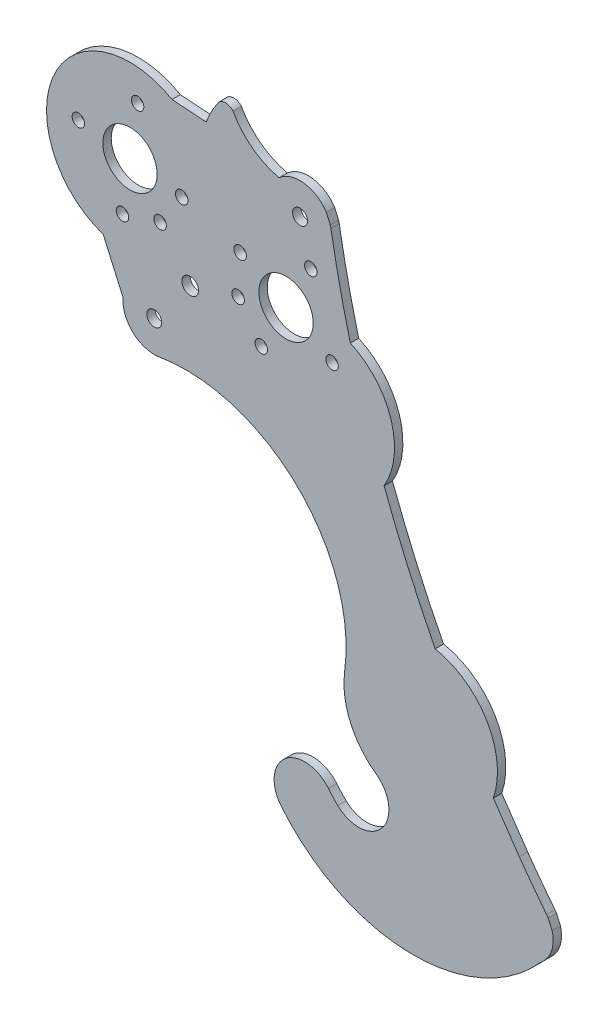
SolidWorks part; units mm, degrees
note: The reader was unsure of these and kept them because the rebuilt part matched: shared geometry of "Sketch9<3>", "Sketch16<3>", "Sketch17<2>", "Sketch20<3>".
material "Plain Carbon Steel"
ref_plane "Front Plane" through (0, 0, 0) normal (0, 0, 1) x (1, 0, 0)
ref_plane "Top Plane" through (0, 0, 0) normal (0, 1, 0) x (1, 0, 0)
ref_plane "Right Plane" through (0, 0, 0) normal (1, 0, 0) x (0, 0, -1)
sketch "Sketch1" plane through (0, 0, 0) normal (0, 0, 1) x (1, 0, 0)
  line L0 (214.9509, 33.6169) -> (221.8072, 36.6569)
  line L1 (221.8072, 36.6569) -> (220.1858, 40.3136)
  line L2 (249.0335, 53.1046) -> (220.1858, 40.3136)
  line L3 (211.0442, 36.2602) -> (218.8806, 18.5866)
  line L4 (213.3296, 37.2735) -> (214.9509, 33.6169)
  line L5 (279.2963, 23.754) -> (254.3124, 52.9018)
  line L6 (223.5, 15.5) -> (275.5, 15.5)
  line L7 (213.3296, 37.2735) -> (211.0442, 36.2602)
  circle A1 centre (275.5, 20.5) radius 1.8
  arc A3 (218.8806, 18.5866) -> (223.5, 15.5) centre (223.5, 20.5) ccw
  circle A4 centre (251.5, 48.5) radius 2.75
  circle A5 centre (223.5, 20.5) radius 1.8
  arc A6 (254.3124, 52.9018) -> (249.0335, 53.1046) centre (251.5791, 50.559) ccw
  arc A7 (275.5, 15.5) -> (279.2963, 23.754) centre (275.5, 20.5) ccw
  dimension "D1" = 5.5
  dimension "D2" = 7.5
  dimension "D3" = 4
extrude "Extrude2" add sketch "Sketch1" along normal blind 2
sketch "Sketch2" plane through (0, 0, 2) normal (0, 0, 1) x (1, 0, 0)
  line L0 (211.0442, 36.2602) -> (218.8806, 18.5866)
  line L1 (211.0442, 36.2602) -> (275.0358, 64.6339)
  line L2 (218.8806, 18.5866) -> (285.1898, 47.9879)
  line L3 (295.3028, 18.9256) -> (275.0358, 64.6339)
  line L4 (285.1898, 47.9879) -> (256.0904, 35.0853)
  line L6 (256.0904, 35.0853) -> (268.5209, 7.0506)
  line L7 (295.3028, 18.9256) -> (268.5209, 7.0506)
  circle A1 centre (256.1616, 71.063) radius 65.1946
  dimension "D1" = 50
  dimension "D2" = 70
extrude "Extrude3" add sketch "Sketch2" against normal blind 2
ref_plane "Plane1" through (11.1049, -25.045, 0) normal (-0.4053, 0.9142, 0) x (-0.9142, -0.4053, 0)
mirror "Mirror2" about plane through (11.1049, -25.045, 0) normal (-0.4053, 0.9142, 0) of bodies 102 103
sketch "Sketch3" plane through (0, 0, 2) normal (0, 0, 1) x (1, 0, 0)
  line L0 (275.0358, 64.6339) -> (254.7689, 110.3422)
  line L1 (211.0442, 36.2602) -> (190.7772, 81.9685)
  line L2 (190.7772, 81.9685) -> (199.9189, 86.0219)
  line L3 (199.9189, 86.0219) -> (220.1858, 40.3136)
  line L4 (220.1858, 40.3136) -> (211.0442, 36.2602)
  line L5 (211.0442, 36.2602) -> (210.9159, 37.0193)
  line L6 (220.1858, 40.3136) -> (275.0358, 64.6339)
  line L7 (199.9189, 86.0219) -> (254.7689, 110.3422)
  line L8 (234.5019, 156.0506) -> (254.7689, 110.3422) construction
extrude "Extrude4" add sketch "Sketch3" against normal blind 2
sketch "Sketch4" plane through (0, 0, 2) normal (0, 0, 1) x (1, 0, 0)
  line L0 (295.3028, 18.9256) -> (234.5019, 156.0506) construction
  line L1 (262.4068, 78.1774) -> (258.7501, 76.556)
  line L2 (262.4068, 78.1774) -> (256.3267, 91.8899)
  line L3 (256.3267, 91.8899) -> (252.67, 90.2685)
  line L4 (258.7501, 76.556) -> (252.67, 90.2685)
  line L5 (286.7271, 23.3274) -> (283.0705, 21.706)
  line L6 (286.7271, 23.3274) -> (280.647, 37.0399)
  line L7 (280.647, 37.0399) -> (276.9904, 35.4185)
  line L8 (283.0705, 21.706) -> (276.9904, 35.4185)
  line L9 (234.4298, 131.406) -> (238.0864, 133.0273)
  line L10 (234.4298, 131.406) -> (228.3497, 145.1185)
  line L11 (228.3497, 145.1185) -> (232.0064, 146.7398)
  line L12 (238.0864, 133.0273) -> (232.0064, 146.7398)
  line L14 (256.3267, 91.8899) -> (238.0864, 133.0273) construction
  line L15 (262.4068, 78.1774) -> (280.647, 37.0399) construction
  line L16 (264.9023, 87.4881) -> (200.9107, 59.1144) construction
  line L17 (182.9408, 99.6421) -> (218.8806, 18.5866) construction
  line L18 (255.7101, 83.4123) -> (259.3667, 85.0336) construction
  circle A2 centre (227.0101, 103.7323) radius 2.75 construction
  dimension "D5" = 18
  dimension "D2" = 45
  dimension "D3" = 4
  dimension "D4" = 15
extrude "Extrude5" cut sketch "Sketch4" against normal blind 10
sketch "Sketch5" plane through (0, 0, 2) normal (0, 0, 1) x (1, 0, 0)
  line L0 (251.5, 48.5) -> (227.0101, 103.7323) construction
  circle A0 centre (239.2551, 76.1162) radius 3
extrude "Extrude6" cut sketch "Sketch5" against normal blind 55
sketch "Sketch8" plane through (0, 0, 0) normal (0, 0, -1) x (-1, 0, 0)
  line L0 (-198.7245, 91.591) -> (-189.7673, 87.7708)
  line L1 (-198.7245, 91.591) -> (-219.7201, 42.3643)
  line L2 (-189.7673, 87.7708) -> (-210.763, 38.544)
  line L3 (-219.7201, 42.3643) -> (-210.763, 38.544)
extrude "Boss-Extrude2" add sketch "Sketch8" against normal blind 2
sketch "Sketch6" plane through (0, 0, 2) normal (0, 0, 1) x (1, 0, 0)
  line L0 (215.3057, 32.6803) -> (222.1619, 35.7203)
  line L1 (215.3057, 32.6803) -> (213.6843, 36.3369)
  line L2 (222.1619, 35.7203) -> (220.5406, 39.377)
  line L3 (213.6843, 36.3369) -> (220.5406, 39.377)
  line L4 (220.1858, 40.3136) -> (213.3296, 37.2735) construction
  line L6 (276.9904, 35.4185) -> (283.0705, 21.706) construction
  line L7 (258.7501, 76.556) -> (262.4068, 78.1774) construction
  dimension "D1" = 18.5
  dimension "D2" = 4
  dimension "D3" = 7.5
  dimension "D4" = 50
extrude "Cut-Extrude2" cut sketch "Sketch6" against normal blind 10
sketch "Sketch7" plane through (0, 0, 0) normal (0, 0, -1) x (-1, 0, 0)
  line L0 (-222.1619, 35.7203) -> (-215.3057, 32.6803)
  line L1 (-222.1619, 35.7203) -> (-220.5406, 39.377)
  line L2 (-215.3057, 32.6803) -> (-213.6843, 36.3369)
  line L3 (-220.5406, 39.377) -> (-213.6843, 36.3369)
  line L4 (-222.1619, 35.7203) -> (-221.7566, 36.6345) construction
  line L5 (-215.3057, 32.6803) -> (-222.1619, 35.7203) construction
  line L6 (-213.7349, 36.3594) -> (-213.6843, 36.3369) construction
  line L7 (-211.7989, 37.4505) -> (-220.5406, 42.0862)
  line L8 (-211.7989, 37.4505) -> (-215.828, 29.8527)
  line L9 (-220.5406, 42.0862) -> (-224.5697, 34.4884)
  line L10 (-215.828, 29.8527) -> (-224.5697, 34.4884)
mirror "Mirror3" about plane through (11.1049, -25.045, 0) normal (-0.4053, 0.9142, 0) of "Cut-Extrude2"
extrude "Boss-Extrude3" add sketch "Sketch7" against normal blind 2
sketch "Sketch9" plane through (0, 0, 0) normal (0, 0, -1) x (-1, 0, 0)
  circle A0 centre (-187.4603, 101.7809) radius 7.5
  circle A1 centre (-222.3731, 140.3178) radius 7.5
  circle A2 centre (-223.5, 20.5) radius 7.5
  circle A3 centre (-275.5, 20.5) radius 7.5
  circle A4 centre (-227.0101, 103.7323) radius 10
  circle A5 centre (-239.2551, 76.1162) radius 10
  circle A6 centre (-251.5, 48.5) radius 10
  arc A7 (-217.2457, 134.8443) -> (-192.4025, 107.4222) centre (-204.5955, 121.3403) ccw
  arc A8 (-188.6919, 94.3827) -> (-218.8442, 26.3799) centre (-194.9996, 56.4934) ccw
  arc A9 (-229.7628, 141.5991) -> (-281.411, 25.1162) centre (-487.8726, 186.3525) cw
  arc A10 (-230.999, 20.375) -> (-268.001, 20.375) centre (-249.5, 20.0666) ccw
  arc M7 (-182.5262, 102.5901) -> (-234.5019, 156.0506) centre (-246.8612, 92.0382) ccw
  line M8 (-234.5019, 156.0506) -> (-295.3028, 18.9256)
  arc M9 (-295.3028, 18.9256) -> (-220.787, 16.3) centre (-256.1616, 71.063) ccw
  arc M10 (-220.787, 16.3) -> (-218.8806, 18.5866) centre (-223.5, 20.5) ccw
  line M11 (-218.8806, 18.5866) -> (-182.9408, 99.6421)
  arc M12 (-182.9408, 99.6421) -> (-182.5262, 102.5901) centre (-187.4603, 101.7809) ccw
  line M13 (-258.7501, 76.556) -> (-262.4068, 78.1774)
  line M14 (-262.4068, 78.1774) -> (-256.3267, 91.8899)
  line M15 (-256.3267, 91.8899) -> (-252.67, 90.2685)
  line M16 (-252.67, 90.2685) -> (-258.7501, 76.556)
  line M17 (-283.0705, 21.706) -> (-286.7271, 23.3274)
  line M18 (-286.7271, 23.3274) -> (-280.647, 37.0399)
  line M19 (-280.647, 37.0399) -> (-276.9904, 35.4185)
  line M20 (-276.9904, 35.4185) -> (-283.0705, 21.706)
  line M21 (-232.0064, 146.7398) -> (-228.3497, 145.1185)
  line M22 (-228.3497, 145.1185) -> (-234.4298, 131.406)
  line M23 (-234.4298, 131.406) -> (-238.0864, 133.0273)
  line M24 (-238.0864, 133.0273) -> (-232.0064, 146.7398)
  line M26 (-190.9853, 87.5303) -> (-192.6067, 83.8736)
  line M27 (-192.6067, 83.8736) -> (-199.4629, 86.9136)
  line M28 (-199.4629, 86.9136) -> (-197.8416, 90.5703)
  line M29 (-197.8416, 90.5703) -> (-190.9853, 87.5303)
  line M30 (-222.1619, 35.7203) -> (-220.5406, 39.377)
  line M31 (-220.5406, 39.377) -> (-213.6843, 36.3369)
  line M32 (-213.6843, 36.3369) -> (-215.3057, 32.6803)
  line M33 (-215.3057, 32.6803) -> (-222.1619, 35.7203)
  dimension "D1" = 15
  dimension "D2" = 20
extrude "Cut-Extrude3" cut sketch "Sketch9" against normal blind 10 contours A2 A10 A3 A9 A1 A7 A0 M20 M17 M18 M19 M22 M23 M24 M21 M7 M8 M9 M16 M13 M14 M15 | A0 A8 A2 M11 M33 M30 M31 M32 M29 M26 M27 M28
extrude "Boss-Extrude4" add sketch "Sketch9<3>" against normal blind 2 contours A0 M11 M7 M12 | A2 M9 M11 M10
sketch "Sketch9<3>" plane through (0, 0, 0) normal (0, 0, -1) x (-1, 0, 0) same geometry as "Sketch9"
sketch "Sketch10" plane through (0, 0, 0) normal (0, 0, -1) x (-1, 0, 0)
  line L0 (-187.4603, 101.7809) -> (-223.5, 20.5) construction
  line L1 (-223.5, 20.5) -> (-205.4801, 61.1404) construction
  line L2 (-205.4801, 61.1404) -> (-258.1527, 84.4953) construction
  arc A0 (-211.0121, 103.9849) -> (-222.9768, 119.2156) centre (-227.0101, 103.7323) ccw construction
  arc A1 (-209.0138, 103.3719) -> (-223.0991, 121.3023) centre (-227.0101, 103.7323) ccw
  arc A2 (-213.0577, 104.885) -> (-222.5865, 117.0151) centre (-227.0101, 103.7323) ccw
  arc A3 (-223.0991, 121.3023) -> (-222.5865, 117.0151) centre (-204.5955, 121.3403) ccw
  circle A4 centre (-227.0101, 103.7323) radius 18 construction
  circle A5 centre (-227.0101, 103.7323) radius 16 construction
  circle A6 centre (-227.0101, 103.7323) radius 14 construction
  arc A7 (-213.0577, 104.885) -> (-209.0138, 103.3719) centre (-204.5955, 121.3403) ccw
  arc A8 (-240.9461, 36.4744) -> (-260.2666, 35.1154) centre (-251.5, 48.5) cw construction
  arc A9 (-242.9866, 37.386) -> (-239.1501, 35.4049) centre (-249.5, 20.0666) cw
  arc A10 (-261.8951, 33.8051) -> (-258.3738, 36.3036) centre (-249.5, 20.0666) cw
  arc A11 (-242.9866, 37.386) -> (-258.3738, 36.3036) centre (-251.5, 48.5) cw
  arc A12 (-239.1501, 35.4049) -> (-261.8951, 33.8051) centre (-251.5, 48.5) cw
  arc A13 (-234.4184, 120.1371) -> (-242.5117, 94.5835) centre (-227.0101, 103.7323) ccw
  arc A14 (-235.9587, 114.499) -> (-240.5254, 100.0803) centre (-227.0101, 103.7323) ccw
  arc A15 (-281.411, 25.1162) -> (-229.7628, 141.5991) centre (-487.8726, 186.3525) ccw construction
  arc A16 (-268.6314, 42.976) -> (-255.1276, 66.1307) centre (-251.5, 48.5) cw
  arc A17 (-213.0577, 104.885) -> (-222.5865, 117.0151) centre (-227.0101, 103.7323) ccw
  arc A18 (-209.0138, 103.3719) -> (-223.0991, 121.3023) centre (-227.0101, 103.7323) ccw
  arc A19 (-265.4873, 47.903) -> (-257.8677, 60.9681) centre (-251.5, 48.5) cw
  arc A20 (-235.9587, 114.499) -> (-234.4184, 120.1371) centre (-239.2163, 118.4185) ccw
  arc A21 (-242.5117, 94.5835) -> (-240.5254, 100.0803) centre (-244.8427, 98.5331) ccw
  arc A22 (-257.8677, 60.9681) -> (-255.1276, 66.1307) centre (-260.1858, 65.5068) ccw
  arc A23 (-268.6314, 42.976) -> (-265.4873, 47.903) centre (-265.0225, 44.1397) ccw
  arc M4 (-192.4025, 107.4222) -> (-217.2457, 134.8443) centre (-204.5955, 121.3403) cw
  arc M12 (-268.001, 20.375) -> (-230.999, 20.375) centre (-249.5, 20.0666) cw
  dimension "D1" = 32
  dimension "D2" = 2
  dimension "D3" = 2
extrude "Boss-Extrude5" add sketch "Sketch10" against normal blind 2 contours A14 A20 A13 A21 | A2 A1 M4 | A12 A11 M12 | A23 A19 A22 A16
sketch "Sketch11" plane through (0, 0, 0) normal (0, 0, -1) x (-1, 0, 0)
  line L0 (-215.1923, 111.2382) -> (-221.6681, 90.7916) construction
  line L1 (-226.4188, 89.7448) -> (-244.17, 109.1672) construction
  line L2 (-244.17, 109.1672) -> (-218.4742, 114.829) construction
  line L3 (-227.0101, 103.7323) -> (-233.6834, 105.8459) construction
  arc A1 (-213.0586, 104.8959) -> (-224.5994, 117.5232) centre (-227.0101, 103.7323) ccw
  arc A2 (-216.2723, 94.7491) -> (-232.9782, 91.0681) centre (-223.1369, 86.154) ccw
  arc A3 (-224.5994, 117.5232) -> (-213.0586, 104.8959) centre (-213.7235, 115.8758) ccw
  arc A4 (-240.1588, 98.9246) -> (-234.9936, 115.2329) centre (-244.17, 109.1672) ccw
  arc A5 (-209.0138, 103.3719) -> (-223.0991, 121.3023) centre (-227.0101, 103.7323) ccw construction
  arc A6 (-232.9782, 91.0681) -> (-216.2723, 94.7491) centre (-227.0101, 103.7323) ccw
  arc A7 (-234.9936, 115.2329) -> (-240.1588, 98.9246) centre (-227.0101, 103.7323) ccw
  circle A8 centre (-227.0101, 103.7323) radius 3
  dimension "D2" = 6
  dimension "D1" = 7
extrude "Cut-Extrude4" cut sketch "Sketch11" against normal blind 10
sketch "Sketch13" plane through (0, 0, 0) normal (0, 0, -1) x (-1, 0, 0)
  line L0 (-220.2817, 120.4274) -> (-222.3731, 140.3178) construction
  line L1 (-222.3731, 140.3178) -> (-207.2338, 151.3182) construction
  line L2 (-220.2817, 120.4274) -> (-215.284, 117.3887)
  line L3 (-230.0726, 145.8144) -> (-230.0212, 145.9081)
  line L4 (-230.0726, 145.8144) -> (-234.4184, 120.1371)
  line L5 (-234.4184, 120.1371) -> (-227.995, 140.6634)
  arc A0 (-217.6542, 118.8298) -> (-204.5753, 153.2498) centre (-222.3731, 140.3178) ccw construction
  arc A1 (-204.5753, 153.2498) -> (-230.0726, 145.8144) centre (-221.0416, 162.2808) cw construction
  arc A2 (-215.284, 117.3887) -> (-202.9573, 154.4255) centre (-222.3731, 140.3178) ccw
  arc A3 (-206.3289, 154.2116) -> (-227.4981, 146.7924) centre (-221.0416, 162.2808) cw
  arc A4 (-220.2817, 120.4274) -> (-203.346, 146.4798) centre (-222.3731, 140.3178) ccw
  arc A5 (-206.3289, 154.2116) -> (-229.1109, 147.568) centre (-221.0416, 162.2808) cw construction
  arc A6 (-209.0138, 103.3719) -> (-223.0991, 121.3023) centre (-227.0101, 103.7323) ccw construction
  circle A7 centre (-222.3731, 140.3178) radius 24 construction
  circle A8 centre (-222.3731, 140.3178) radius 22 construction
  circle A9 centre (-222.3731, 140.3178) radius 20 construction
  arc A10 (-202.9573, 154.4255) -> (-206.3289, 154.2116) centre (-204.5361, 152.6327) ccw
  arc A11 (-206.6353, 147.3049) -> (-225.6434, 142.0164) centre (-221.0416, 162.2808) cw
  arc A12 (-230.0212, 145.9081) -> (-227.4981, 146.7924) centre (-228.2677, 144.9463) cw
  arc A13 (-203.346, 146.4798) -> (-206.6353, 147.3049) centre (-205.2487, 145.8636) ccw
  arc A14 (-225.6434, 142.0164) -> (-227.995, 140.6634) centre (-226.0863, 140.0661) ccw
  circle M8 centre (-222.3731, 140.3178) radius 1.8
  arc M27 (-209.0138, 103.3719) -> (-223.0991, 121.3023) centre (-227.0101, 103.7323) ccw
  arc M29 (-217.2457, 134.8443) -> (-228.6758, 144.3831) centre (-222.3731, 140.3178) ccw
  line M30 (-228.6758, 144.3831) -> (-229.6175, 142.2592)
  arc M31 (-229.6175, 142.2592) -> (-229.7628, 141.5991) centre (-222.3731, 140.3178) ccw
  arc M32 (-229.7628, 141.5991) -> (-234.4184, 120.1371) centre (-487.8726, 186.3525) cw
  dimension "D1" = 44
  dimension "D2" = 2
  dimension "D6" = 2
  dimension "D5" = 120
  dimension "D3" = 2
  dimension "D4" = 2
extrude "Boss-Extrude6" add sketch "Sketch13" against normal blind 2 contours A14 A11 A3 L5 M8 M29 M30 M31 M32 | A13 A4 A2 A10 A3 A11 M27 M29
sketch "Sketch14" plane through (0, 0, 0) normal (0, 0, -1) x (-1, 0, 0)
  line L0 (-204.6205, 124.1671) -> (-201.4385, 128.5814)
  line L1 (-187.4603, 109.2809) -> (-192.368, 107.4522)
  arc A0 (-187.4603, 109.2809) -> (-201.4385, 128.5814) centre (-176.6451, 131.8258) cw
  arc A1 (-188.6919, 94.3827) -> (-192.4025, 107.4222) centre (-187.4603, 101.7809) ccw construction
  arc A3 (-192.368, 107.4522) -> (-204.6205, 124.1671) centre (-176.6451, 131.8258) cw
  arc A4 (-187.4603, 109.2809) -> (-199.8399, 141.166) centre (-176.6451, 131.8258) cw construction
  arc A5 (-189.1904, 105.6744) -> (-203.5504, 142.6601) centre (-176.6451, 131.8258) cw construction
  dimension "D1" = 4
extrude "Boss-Extrude7" add sketch "Sketch14" against normal blind 2
mirror "Mirror5" about plane through (11.1049, -25.045, 0) normal (-0.4053, 0.9142, 0) of "Cut-Extrude4", "Boss-Extrude6", "Boss-Extrude7"
sketch "Sketch16" plane through (0, 0, 0) normal (0, 0, -1) x (-1, 0, 0)
  line L0 (-227.0101, 103.7323) -> (-196.0677, 112.8223)
  circle A0 centre (-196.0677, 112.8223) radius 2
  circle A1 centre (-187.4603, 101.7809) radius 1.8 construction
  circle A2 centre (-196.0677, 112.8223) radius 3.3422
  dimension "D2" = 4
  dimension "D3" = 14
  dimension "D1" = 32.25
extrude "Boss-Extrude8" add sketch "Sketch16" against normal blind 2
extrude "Cut-Extrude5" cut sketch "Sketch16<3>" against normal blind 2
sketch "Sketch16<3>" plane through (0, 0, 0) normal (0, 0, -1) x (-1, 0, 0) same geometry as "Sketch16"
sketch "Sketch17" plane through (0, 0, 0) normal (0, 0, -1) x (-1, 0, 0)
  line L0 (-227.0101, 103.7323) -> (-251.5, 48.5) construction
  line L1 (-204.6076, 125.0508) -> (-197.9558, 111.3332)
  line L2 (-197.9558, 111.3332) -> (-189.8837, 107.7486)
  line L3 (-191.7097, 149.3004) -> (-199.8952, 148.7288)
  line L4 (-189.8837, 107.7486) -> (-207.1736, 97.4)
  line L5 (-207.1736, 97.4) -> (-213.2426, 101.1916)
  line L6 (-204.6076, 125.0508) -> (-199.8952, 145.4392)
  line L7 (-175.2396, 113.0687) -> (-179.9834, 102.3699)
  line L8 (-196.0677, 112.8223) -> (-181.6542, 132.0121) construction
  line L9 (-199.8952, 145.4392) -> (-204.2733, 150.4745)
  line L10 (-204.2733, 150.4745) -> (-216.9035, 142.2081)
  line L11 (-216.9035, 142.2081) -> (-223.5, 134.1176)
  line L12 (-196.0677, 112.8223) -> (-188.8609, 122.4172) construction
  line L13 (-196.0677, 112.8223) -> (-207.5488, 116.3127) construction
  circle A0 centre (-181.6542, 132.0121) radius 12.5 construction
  circle A1 centre (-179.8489, 119.6432) radius 1.5
  circle A2 centre (-194.0231, 130.2069) radius 1.5
  circle A3 centre (-183.4594, 144.3811) radius 1.5
  circle A4 centre (-169.2852, 133.8174) radius 1.5
  arc A5 (-175.2396, 113.0687) -> (-191.7097, 149.3004) centre (-181.6542, 132.0121) ccw
  circle A6 centre (-181.6542, 132.0121) radius 6.5
  circle A7 centre (-187.4603, 101.7809) radius 1.8
  circle A8 centre (-196.0677, 112.8223) radius 2
  circle A9 centre (-222.3731, 140.3178) radius 1.8
  circle A10 centre (-223.5, 20.5) radius 1.8
  circle A11 centre (-275.5, 20.5) radius 1.8
  circle A17 centre (-188.8609, 122.4172) radius 1.5
  circle A18 centre (-207.5488, 116.3127) radius 1.5
  circle A19 centre (-208.0244, 125.73) radius 1.5
  circle A20 centre (-213.1032, 108.7976) radius 1.5
  circle A21 centre (-230.0356, 113.8764) radius 1.5
  circle A22 centre (-224.9568, 130.8088) radius 1.5
  circle A23 centre (-219.03, 119.8032) radius 6.5
  arc A32 (-179.9834, 102.3699) -> (-187.4603, 109.2809) centre (-187.4603, 101.7809) ccw
  arc A33 (-223.5, 134.1176) -> (-233.5627, 116.1042) centre (-219.03, 119.8032) ccw
  circle A35 centre (-239.2551, 76.1162) radius 3
  circle A36 centre (-251.5, 48.5) radius 14
  arc A37 (-201.4385, 128.5814) -> (-202.9573, 154.4255) centre (-222.3731, 140.3178) ccw
  arc A38 (-201.4385, 128.5814) -> (-196.1372, 116.1638) centre (-176.6451, 131.8258) ccw
  arc A39 (-192.7285, 112.6799) -> (-196.1372, 116.1638) centre (-196.0677, 112.8223) ccw
  arc A40 (-192.7285, 112.6799) -> (-187.4603, 109.2809) centre (-176.6451, 131.8258) ccw
  arc A41 (-188.6919, 94.3827) -> (-187.4603, 109.2809) centre (-187.4603, 101.7809) ccw
  arc A42 (-201.4385, 128.5814) -> (-199.8952, 148.7288) centre (-222.3731, 140.3178) ccw
  arc A43 (-201.4385, 128.5814) -> (-196.1372, 116.1638) centre (-176.6451, 131.8258) ccw
  arc A44 (-192.7285, 112.6799) -> (-196.1372, 116.1638) centre (-196.0677, 112.8223) ccw
  arc A45 (-192.7285, 112.6799) -> (-187.4603, 109.2809) centre (-176.6451, 131.8258) ccw
  arc A46 (-233.5627, 116.1042) -> (-213.2426, 101.1916) centre (-227.0101, 103.7323) ccw
  point P10 (-239.2551, 76.1162)
  dimension "D3" = 25
  dimension "D4" = 3
  dimension "D6" = 40
  dimension "D7" = 13
  dimension "D10" = 3
  dimension "D1" = 30
  dimension "D2" = 24
  dimension "D9" = 0
  dimension "D12" = 110
  dimension "D5" = 4
  dimension "D11" = 2
extrude "Boss-Extrude9" add sketch "Sketch17" against normal blind 2
extrude "Cut-Extrude6" cut sketch "Sketch17<2>" against normal blind 2
sketch "Sketch17<2>" plane through (0, 0, 0) normal (0, 0, -1) x (-1, 0, 0) same geometry as "Sketch17"
sketch "Sketch20" plane through (0, 0, 0) normal (0, 0, -1) x (-1, 0, 0)
  line L0 (-268.6314, 42.976) -> (-280.1153, 26.2004)
  line L1 (-205.8019, 22.7166) -> (-233.0578, 51.3015)
  line L2 (-205.8019, 22.7166) -> (-251.2764, -34.343)
  line L3 (-251.2764, -34.343) -> (-297.5933, 8.0973)
  line L4 (-297.5933, 8.0973) -> (-277.1397, 11.5556)
  arc A0 (-275.5, 20.5) -> (-223.5, 20.5) centre (-249.5, 41.5507) ccw construction
  arc A1 (-281.2004, 15.8847) -> (-217.7996, 15.8847) centre (-249.5, 41.5507) ccw
  arc A2 (-231.4037, 22.7166) -> (-229.2004, 25.1153) centre (-249.5, 41.5507) ccw
  arc A3 (-280.1153, 26.2004) -> (-281.2004, 15.8847) centre (-275.5, 20.5) ccw
  arc A4 (-217.7996, 15.8847) -> (-229.2004, 25.1153) centre (-223.5, 20.5) ccw
  arc A5 (-240.616, 33.8346) -> (-231.4037, 22.7166) centre (-236.4191, 27.9365) ccw
  arc A7 (-253.7477, 30.6409) -> (-239.1501, 35.4049) centre (-251.5, 48.5) ccw construction
  arc A8 (-188.6919, 94.3827) -> (-218.8442, 26.3799) centre (-194.9996, 56.4934) ccw construction
  arc A14 (-229.0582, 15.4645) -> (-218.8442, 26.3799) centre (-223.5, 20.5) ccw construction
  circle A15 centre (-223.5, 20.5) radius 1.8
  circle A16 centre (-275.5, 20.5) radius 1.8
  arc A17 (-240.616, 33.8346) -> (-268.6851, 42.8977) centre (-251.2764, 48.8162) ccw
  point P3 (-249.5, 8.0973)
  dimension "D2" = 102.01
extrude "Boss-Extrude11" add sketch "Sketch20" against normal blind 2
extrude "Cut-Extrude8" cut sketch "Sketch20<3>" against normal blind 2
sketch "Sketch20<3>" plane through (0, 0, 0) normal (0, 0, -1) x (-1, 0, 0) same geometry as "Sketch20"
sketch "Sketch21" plane through (0, 0, 2) normal (0, 0, 1) x (1, 0, 0)
  arc A0 (234.4184, 120.1371) -> (208.4895, 92.4574) centre (215.7019, 111.6855) cw
  arc A1 (233.0578, 51.3015) -> (188.6919, 94.3827) centre (194.9996, 56.4934) ccw construction
extrude "Cut-Extrude9" [suppressed] cut sketch "Sketch21" against normal through all and the other way through all
